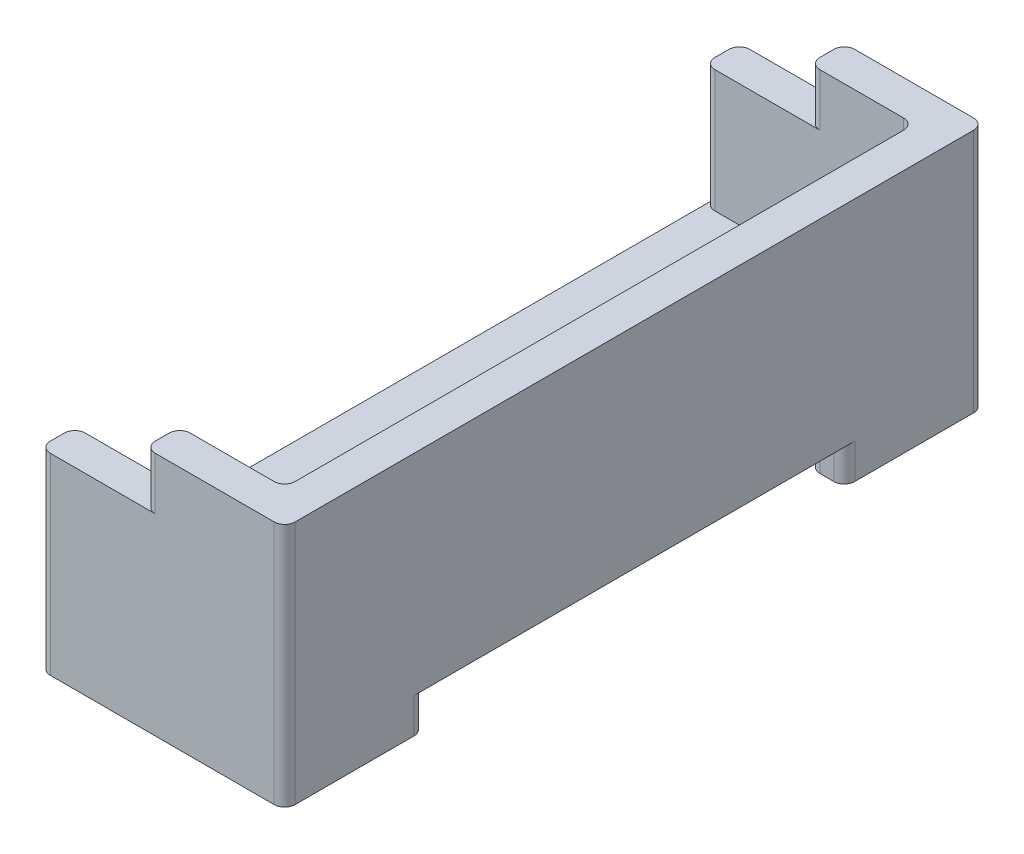
SolidWorks part; units mm, degrees
other "Markup1"
sketch "Sketch9" plane through (-31, 0, 0) normal (-0.2348, 0.9689, 0.0787) x (0.6754, 0.1044, 0.7301)
material "PLA"
ref_plane "Front Plane" through (0, 0, 0) normal (0, 0, 1) x (1, 0, 0)
ref_plane "Top Plane" through (0, 0, 0) normal (0, 1, 0) x (1, 0, 0)
ref_plane "Right Plane" through (0, 0, 0) normal (1, 0, 0) x (0, 0, -1)
sketch "Sketch1" plane through (0, 0, 0) normal (0, 1, 0) x (1, 0, 0)
  line L0 (0, 200) -> (0, 0)
  line L1 (270, 200) -> (270, 0)
  line L6 (0, 200) -> (270, 200)
  line L12 (270, 0) -> (0, 0)
  dimension "D1" = 270
  dimension "D2" = 200
  dimension "D5" = 0
  dimension "D11" = 270
extrude "Boss-Extrude1" add sketch "Sketch1" against normal blind 10 contours L0 L12 L1 L6
sketch "Sketch10" plane through (0, 0, 0) normal (0, 1, 0) x (1, 0, 0)
  line L0 (0, 175) -> (40, 175)
  line L1 (0, 200) -> (0, 0) construction
  line L2 (40, 175) -> (40, 125)
  line L3 (40, 125) -> (0, 125)
  line L4 (0, 125) -> (0, 175)
  line L5 (0, 75) -> (-40, 75)
  line L6 (-40, 75) -> (-40, 25)
  line L7 (-40, 25) -> (0, 25)
  line L8 (0, 25) -> (0, 75)
  line L9 (0, 200) -> (270, 200) construction
  line L10 (270, 0) -> (0, 0) construction
  line M10 (0, 200) -> (0, 0)
  dimension "D1" = 40
  dimension "D2" = 50
  dimension "D3" = 25
  dimension "D4" = 50
  dimension "D5" = 40
  dimension "D6" = 25
extrude "Cut-Extrude1" cut sketch "Sketch10" against normal blind 5 contours L3 L2 L0 M10 region at (20, 0, -150)
extrude "Boss-Extrude2" add sketch "Sketch10<3>" against normal blind 5 contours L6 L7 L5 M10 region at (-20, 0, -50)
sketch "Sketch10<3>" plane through (0, 0, 0) normal (0, 1, 0) x (1, 0, 0) same geometry as "Sketch10"
sketch "Sketch12" plane through (0, -5, 0) normal (0, 1, 0) x (1, 0, 0)
  line L0 (40, 125) -> (0, 125) construction
  line L1 (0, 175) -> (0, 125) construction
  line L2 (0, 75) -> (-40, 75) construction
  line L4 (0, 125) -> (0, 75) construction
  circle A0 centre (25, 150) radius 3
  circle A1 centre (-25, 50) radius 3
  dimension "D3" = 6
  dimension "D4" = 6
  dimension "D5" = 25
  dimension "D6" = 25
  dimension "D1" = 25
  dimension "D2" = 25
extrude "Cut-Extrude2" cut sketch "Sketch12" against normal blind 5 contours A0
extrude "Cut-Extrude3" cut sketch "Sketch12<3>" along normal blind 5 contours A1
sketch "Sketch12<3>" plane through (0, -5, 0) normal (0, 1, 0) x (1, 0, 0) same geometry as "Sketch12"
sketch "Sketch13" plane through (0, 0, 0) normal (0, 1, 0) x (1, 0, 0)
  line L0 (0, 190) -> (260, 190)
  line L1 (0, 200) -> (0, 175) construction
  line L2 (260, 190) -> (260, 10)
  line L3 (260, 10) -> (0, 10)
  line L4 (0, 25) -> (0, 0) construction
  line L5 (0, 10) -> (0, 0)
  line L6 (0, 0) -> (270, 0)
  line L7 (270, 0) -> (270, 200)
  line L8 (270, 200) -> (0, 200)
  line L9 (0, 200) -> (0, 190)
  dimension "D1" = 10
  dimension "D2" = 10
  dimension "D3" = 10
extrude "Boss-Extrude3" add sketch "Sketch13" along normal blind 50
sketch "Sketch14" plane through (0, -10, 0) normal (0, -1, 0) x (1, 0, 0)
  line L1 (0, -200) -> (270, -200) construction
  line L2 (200, -190) -> (260, -190)
  line L3 (260, -190) -> (260, -160)
  line L5 (270, -200) -> (270, 0) construction
  line L6 (270, -160) -> (270, -200)
  line L7 (270, -200) -> (200, -200)
  line L17 (270, 0) -> (200, 0)
  line L18 (270, 0) -> (0, 0) construction
  line L19 (200, 0) -> (200, -10)
  line L20 (200, -10) -> (260, -10)
  line L21 (200, -200) -> (200, -190)
  line L22 (260, -160) -> (270, -160)
  line L23 (270, 0) -> (270, -40)
  line L24 (270, -40) -> (260, -40)
  line L25 (260, -40) -> (260, -10)
  dimension "D1" = 10
  dimension "D2" = 10
  dimension "D3" = 70
  dimension "D4" = 10
  dimension "D5" = 70
  dimension "D6" = 40
  dimension "D7" = 10
  dimension "D8" = 40
sketch "Sketch15" plane through (0, 0, 0) normal (0, 1, 0) x (1, 0, 0)
  line L0 (260, 190) -> (260, 10) construction
  line L3 (260, 10) -> (0, 10) construction
  line L4 (0, 190) -> (260, 190) construction
  circle A0 centre (230, 78.5) radius 2.75
  circle A1 centre (230, 121.5) radius 2.75
  dimension "D2" = 5.5
  dimension "D3" = 5.5
  dimension "D6" = 68.5
  dimension "D1" = 43
  dimension "D4" = 30
  dimension "D5" = 68.5
extrude "Cut-Extrude4" cut sketch "Sketch15" against normal up to next contours A0 | A1
sketch "Sketch16" plane through (0, 0, 0) normal (0, 1, 0) x (1, 0, 0)
  line L0 (260, 10) -> (0, 10) construction
  line L1 (0, 190) -> (260, 190) construction
  line L2 (260, 190) -> (260, 10) construction
  circle A0 centre (230, 143) radius 3
  circle A1 centre (230, 175) radius 3
  circle A2 centre (230, 57) radius 3
  circle A3 centre (230, 25) radius 3
  dimension "D1" = 6
  dimension "D2" = 6
  dimension "D3" = 6
  dimension "D4" = 6
  dimension "D5" = 32
  dimension "D6" = 32
  dimension "D10" = 30
  dimension "D12" = 30
  dimension "D7" = 15
  dimension "D8" = 15
  dimension "D9" = 30
  dimension "D11" = 30
extrude "Cut-Extrude5" cut sketch "Sketch16" against normal up to next
sketch "Sketch17" plane through (0, 50, 0) normal (0, 1, 0) x (1, 0, 0)
  line L0 (230, 0) -> (230, 10)
  line L1 (0, 0) -> (270, 0) construction
  line L2 (260, 10) -> (0, 10) construction
  line L3 (230, 10) -> (0, 10)
  line L4 (0, 10) -> (0, 0)
  line L5 (0, 0) -> (230, 0)
  line L6 (230, 190) -> (230, 200)
  line L7 (0, 190) -> (260, 190) construction
  line L8 (270, 200) -> (0, 200) construction
  line L9 (230, 200) -> (0, 200)
  line L10 (0, 200) -> (0, 190)
  line L11 (0, 190) -> (230, 190)
  point P6 (230, 5)
  dimension "D1" = 230
extrude "Cut-Extrude6" cut sketch "Sketch17" against normal blind 15
sketch "Sketch18" plane through (0, 35, 0) normal (0, 1, 0) x (1, 0, 0)
  line L0 (200, 200) -> (-40, 200)
  line L1 (230, 200) -> (0, 200) construction
  line L2 (-40, 200) -> (-40, 0)
  line L3 (-40, 0) -> (200, 0)
  line L4 (0, 0) -> (230, 0) construction
  line L5 (200, 0) -> (200, 200)
  line L7 (0, 10) -> (0, 0) construction
  dimension "D1" = 240
  dimension "D2" = 40
extrude "Cut-Extrude7" cut sketch "Sketch18" against normal up to next
extrude "Boss-Extrude4" add sketch "Sketch14" along normal blind 10
fillet "Fillet1" radius 3 20 edges at (200, 7.5, 0) (200, -15, -10) (260, -15, -10) (260, -15, -40) (270, -15, -40) (260, -15, -160) (270, -15, -160) (270, 15, -200) (200, 7.5, -200) (200, -15, -190) (260, -15, -190) (200, 17.5, -10) (230, 42.5, 0) (230, 42.5, -10) (260, 25, -10) (260, 25, -190) (230, 42.5, -200) (230, 42.5, -190) (200, 17.5, -190) (270, 15, 0)
